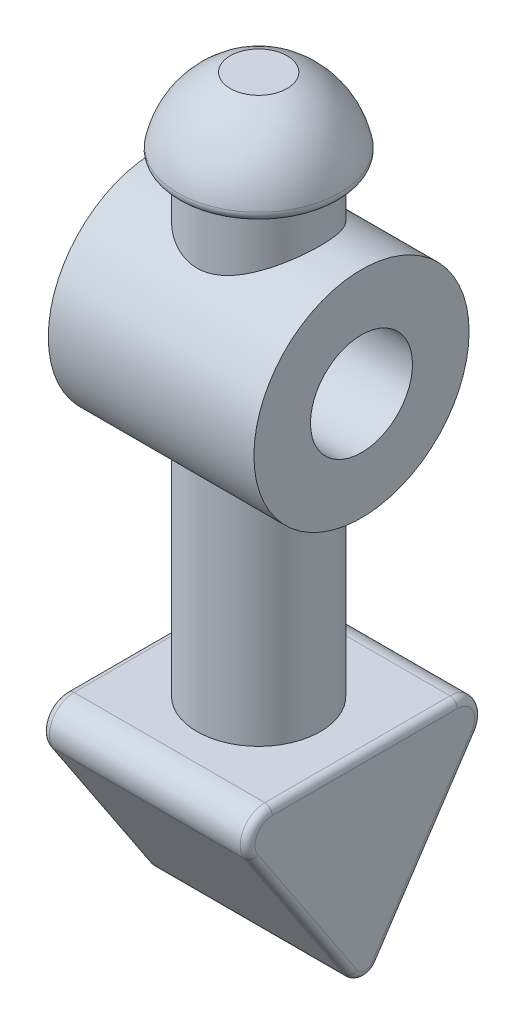
SolidWorks part; units mm, degrees
material "ABS"
ref_plane "Front Plane" through (0, 0, 0) normal (0, 0, 1) x (1, 0, 0)
ref_plane "Top Plane" through (0, 0, 0) normal (0, 1, 0) x (1, 0, 0)
ref_plane "Right Plane" through (0, 0, 0) normal (1, 0, 0) x (0, 0, -1)
sketch "Sketch1" plane through (0, 0, 0) normal (1, 0, 0) x (0, 0, -1)
  circle A0 centre (0, 0) radius 16.6116
  dimension "D1" = 33.2232
extrude "Boss-Extrude1" add sketch "Sketch1" along normal blind 31.75
ref_plane "Plane1" through (2.54, 0, 0) normal (1, 0, 0) x (0, 0, -1)
ref_plane "Plane2" through (29.21, 0, 0) normal (1, 0, 0) x (0, 0, -1)
sketch "Sketch5" plane through (0, 0, 0) normal (-1, 0, 0) x (0, 0, 1)
  circle A0 centre (0, 0) radius 7.874
  dimension "D1" = 15.748
extrude "Cut-Extrude4" cut sketch "Sketch5" against normal up to surface (31.75 mm away) up to face at (31.75, 0, -16.6116)
ref_plane "Plane4" through (0, 16.6116, 0) normal (0, 1, 0) x (1, 0, 0)
ref_plane "Plane5" through (0, 23.6322, 0) normal (0, 1, 0) x (1, 0, 0)
sketch "Sketch7" plane through (0, 23.6322, 0) normal (0, 1, 0) x (1, 0, 0)
  line L0 (15.875, 15.7988) -> (15.875, -15.7988) construction
  circle A0 centre (15.875, 0) radius 9.525
  dimension "D1" = 19.05
extrude "Boss-Extrude2" add sketch "Sketch7" against normal blind 14.732
sketch "Sketch8" plane through (0, 23.6322, 0) normal (0, 1, 0) x (1, 0, 0)
  circle A0 centre (15.875, 0) radius 12.7
  dimension "D1" = 25.4
extrude "Boss-Extrude3" add sketch "Sketch8" along normal blind 11.43
sketch "Sketch9" plane through (0, 35.0622, 0) normal (0, 1, 0) x (1, 0, 0)
  circle A0 centre (15.875, 0) radius 6.858
sketch "Sketch10" plane through (0, 0, 0) normal (0, 0, 1) x (1, 0, 0)
  line L0 (11.4874, 35.0622) -> (3.175, 35.0622)
  line L1 (3.175, 35.0622) -> (3.175, 23.6322)
  line L2 (15.875, 35.0622) -> (15.875, 19.0536) construction
  line L3 (3.175, 35.0622) -> (3.175, 23.6322) construction
  line L4 (3.175, 23.6322) -> (28.575, 23.6322) construction
  arc A0 (11.4874, 35.0622) -> (3.175, 23.6322) centre (16.76, 22.4901) ccw
  dimension "D1" = 0
revolve "Cut-Revolve1" cut sketch "Sketch10" angle 360 about L2
fillet "Fillet5" radius 1.27 1 edges at (15.875, 23.6322, 12.7)
sketch "Sketch11" plane through (0, 0, 0) normal (0, 0, 1) x (1, 0, 0)
  line L0 (15.875, 35.0622) -> (15.875, -72.8878) construction
ref_plane "Plane6" through (15.875, 0, 0) normal (1, 0, 0) x (0, 0, -1)
sketch "Sketch12" plane through (15.875, 0, 0) normal (1, 0, 0) x (0, 0, -1)
  line L0 (0.5127, -78.534) -> (0.5127, -31.0337) construction
  line L1 (2.6291, -77.3984) -> (7.3131, -70.3406)
  line L2 (-13.7709, -48.3616) -> (14.7981, -48.3616)
  line L3 (-22.9, -16.6116) -> (22.7687, -16.6116) construction
  line L5 (-16.9456, -54.2782) -> (-6.2871, -70.3406)
  line L8 (17.9726, -54.2784) -> (7.3131, -70.3406)
  line L9 (-6.2871, -70.3406) -> (-1.6037, -77.3984)
  arc A0 (17.9726, -54.2784) -> (14.7981, -48.3616) centre (14.7981, -52.1716) ccw
  arc A1 (2.6291, -77.3984) -> (-1.6037, -77.3984) centre (0.5127, -75.994) cw
  arc A2 (-16.9456, -54.2782) -> (-13.7709, -48.3616) centre (-13.7709, -52.1716) cw
  circle A3 centre (0, 0) radius 16.6116 construction
  dimension "D1" = 2.54
  dimension "D2" = 3.81
  dimension "D5" = 7.62
  dimension "D3" = 33.567
  dimension "D4" = 33.57
  dimension "D6" = 28.569
  dimension "D7" = 31.75
extrude "Boss-Extrude4" add sketch "Sketch12" along normal blind 15.875 and the other way blind 15.875 separate body
ref_plane "Plane7" through (0, -16.6116, 0) normal (0, -1, 0) x (-1, 0, 0)
sketch "Sketch13" plane through (0, -16.6116, 0) normal (0, -1, 0) x (-1, 0, 0)
  circle A0 centre (-15.875, 0) radius 9.525
  dimension "D1" = 19.05
extrude "Boss-Extrude5" add sketch "Sketch13" along normal blind 31.75 and the other way blind 3.81
ref_plane "Plane8" through (0, 0, -11.43) normal (0, 0, 1) x (1, 0, 0)
ref_plane "Plane9" through (0, 0, 11.43) normal (0, 0, 1) x (1, 0, 0)
fillet "Fillet6" radius 1.143 12 edges at (0, -65.8384, -10.3009) (31.75, -65.8384, -10.3009) (0, -78.534, -0.5127) (0, -65.8383, 9.2746) (0, -50.3702, 17.1282) (0, -48.3616, -0.5136) (0, -50.3703, -18.1554) (31.75, -78.534, -0.5127) (31.75, -65.8383, 9.2746) (31.75, -50.3702, 17.1282) (31.75, -48.3616, -0.5136) (31.75, -50.3703, -18.1554)
ref_plane "Plane14" through (6.35, 0, 0) normal (1, 0, 0) x (0, 0, -1)
